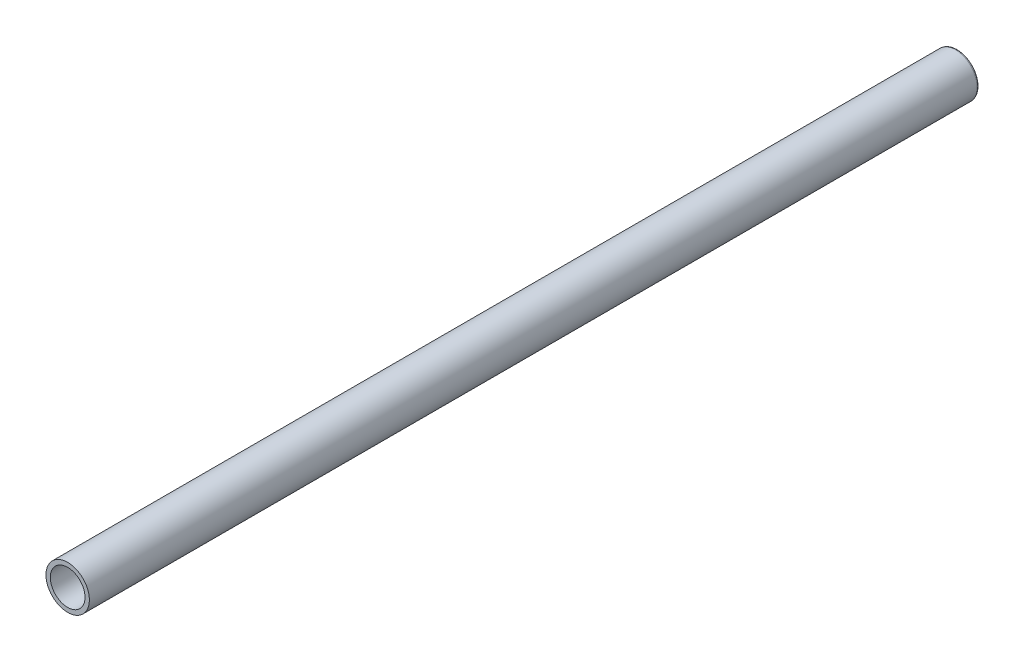
SolidWorks part; units mm, degrees
ref_plane "Piano frontale" through (0, 0, 0) normal (0, 0, 1) x (1, 0, 0)
ref_plane "Piano superiore" through (0, 0, 0) normal (0, 1, 0) x (1, 0, 0)
ref_plane "Piano destro" through (0, 0, 0) normal (1, 0, 0) x (0, 0, -1)
sketch "Schizzo1" plane through (0, 0, 0) normal (1, 0, 0) x (0, 0, -1)
  line L0 (-65.4069, 0) -> (91.3363, 0) construction
  line L1 (-124.6564, 5) -> (80.3436, 5)
  line L2 (-124.6564, 4) -> (80.3436, 4)
  line L3 (-124.6564, 5) -> (-124.6564, 4)
  line L4 (80.3436, 5) -> (80.3436, 4)
  line L5 (55, 0) -> (-55, 0) construction
  line L6 (0, 55) -> (0, -55) construction
  dimension "D2" = 10
  dimension "D3" = 205
  dimension "D4" = 124.6564
  dimension "D1" = 1
revolve "Rivoluzione1" add sketch "Schizzo1" angle 360 about L0
sketch "Schizzo2" plane through (0, 0, 0) normal (0, 1, 0) x (1, 0, 0)
  line L0 (4, 80.3436) -> (-4, 80.3436) construction
  line L1 (0, -55) -> (0, 55) construction
  circle A0 centre (0, 64.3436) radius 1.5
  dimension "D1" = 3
  dimension "D2" = 16
extrude "Taglio-Estrusione1" cut sketch "Schizzo2" against normal blind 10
sketch "Schizzo3" plane through (0, 0, 0) normal (1, 0, 0) x (0, 0, -1)
  line L0 (80.3436, -5) -> (80.3436, 5) construction
  line L1 (55, 0) -> (-55, 0) construction
  circle A0 centre (65.3436, 0) radius 1
  dimension "D1" = 2
  dimension "D2" = 15
extrude "Taglio-Estrusione2" cut sketch "Schizzo3" against normal blind 10
fillet "Raccordo4" radius 0.5 2 edges at (5, 0, -80.3436) (4, 0, -80.3436)
ref_axis "Assi1" through (0, -4.7307, -64.3436) along (0, 1, 0)
ref_axis "Assi2" through (-8.2217, 0, -65.3436) along (1, 0, 0)
